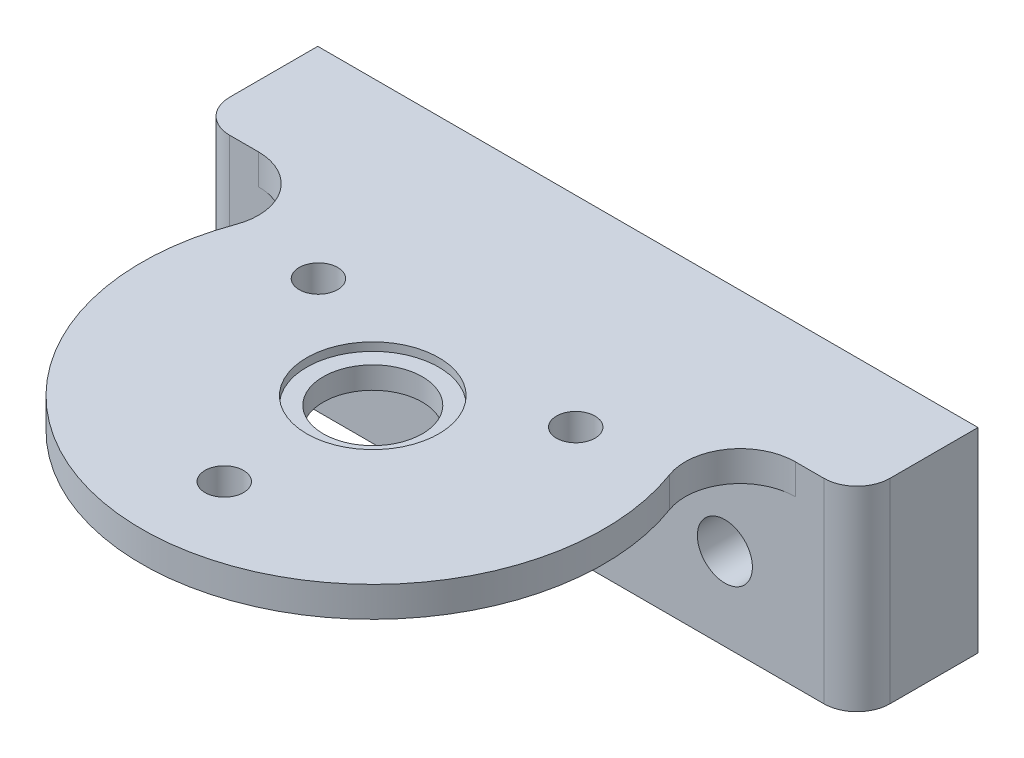
SolidWorks part; units mm, degrees
ref_plane "Front Plane" through (0, 0, 0) normal (0, 0, 1) x (1, 0, 0)
ref_plane "Top Plane" through (0, 0, 0) normal (0, 1, 0) x (1, 0, 0)
ref_plane "Right Plane" through (0, 0, 0) normal (1, 0, 0) x (0, 0, -1)
sketch "Sketch1" plane through (0, 0, 0) normal (0, 1, 0) x (1, 0, 0)
  circle A0 centre (0, 0) radius 6
  circle A1 centre (0, 0) radius 4.5
  circle A2 centre (0, 0) radius 21
  dimension "D1" = 12
  dimension "D2" = 1.5
  dimension "D3" = 15
extrude "Boss-Extrude1" add sketch "Sketch1" along normal blind 2 contours A0 A1 region at (-5.8303, 0, 0)
extrude "Boss-Extrude3" add sketch "Sketch1<5>" along normal offset from surface (2.75 mm away) 0.75 contours A2 A0 region at (-20.406, 0, 0) up to face at (0, 2, 4.5) offset beyond the face yes
sketch "Sketch1<5>" plane through (0, 0, 0) normal (0, 1, 0) x (1, 0, 0) same geometry as "Sketch1"
sketch "Sketch2" plane through (0, 2.75, 0) normal (0, 1, 0) x (1, 0, 0)
  line L0 (0, -6) -> (0, -21) construction
  circle A0 centre (0, 0) radius 6 construction
  circle A1 centre (0, 0) radius 21 construction
  circle A2 centre (0, -13.5) radius 1.75
  dimension "D1" = 3.5
extrude "Cut-Extrude1" cut sketch "Sketch2" against normal blind 4.5
pattern_circular "CirPattern1" count 3 over 360 about axis through (0, 2, 0) along (0, -1, 0) of "Cut-Extrude1"
sketch "Sketch9" plane through (0, 0, 0) normal (0, -1, 0) x (1, 0, 0)
  line L2 (-30, -25) -> (30, -25)
  line L4 (-30, -14) -> (30, -14)
  line L5 (-30, -25) -> (-30, -14)
  line L6 (30, -25) -> (30, -14)
  line L7 (0, 0) -> (0, -25) construction
  line L8 (0, -25) -> (-30, -25) construction
  point P0 (0, 0)
  point P7 (0, -14)
  dimension "D1" = 14
  dimension "D2" = 11
  dimension "D4" = 30
extrude "Boss-Extrude7" add sketch "Sketch9" along normal blind 15 and the other way up to surface (2.75 mm away) other way up to face at (-13.2069, 2.75, -7.625)
sketch "Sketch10" plane through (0, 0, -14) normal (0, 0, 1) x (1, 0, 0)
  line L0 (0, 0) -> (0, -15) construction
  line L3 (-18, -7.5) -> (0, -7.5) construction
  line L5 (30, -15) -> (-30, -15) construction
  line L6 (-15.6525, 0) -> (15.6525, 0) construction
  circle A0 centre (-18, -7.5) radius 2.5
  circle A2 centre (18, -7.5) radius 2.5
  point P6 (0, 0)
  point P9 (0.0683, -12.0212)
  point P11 (0, -15)
  point P12 (0, -3.5324)
  point P15 (0, 0)
  dimension "D2" = 5
  dimension "D1" = 18
extrude "Cut-Extrude3" cut sketch "Sketch10" against normal up to next
fillet "Fillet4" radius 3 2 edges at (-30, -6.125, -14) (30, -6.125, -14)
fillet "Fillet5" radius 5 2 edges at (15.6525, 1.375, -14) (-15.6525, 1.375, -14)
